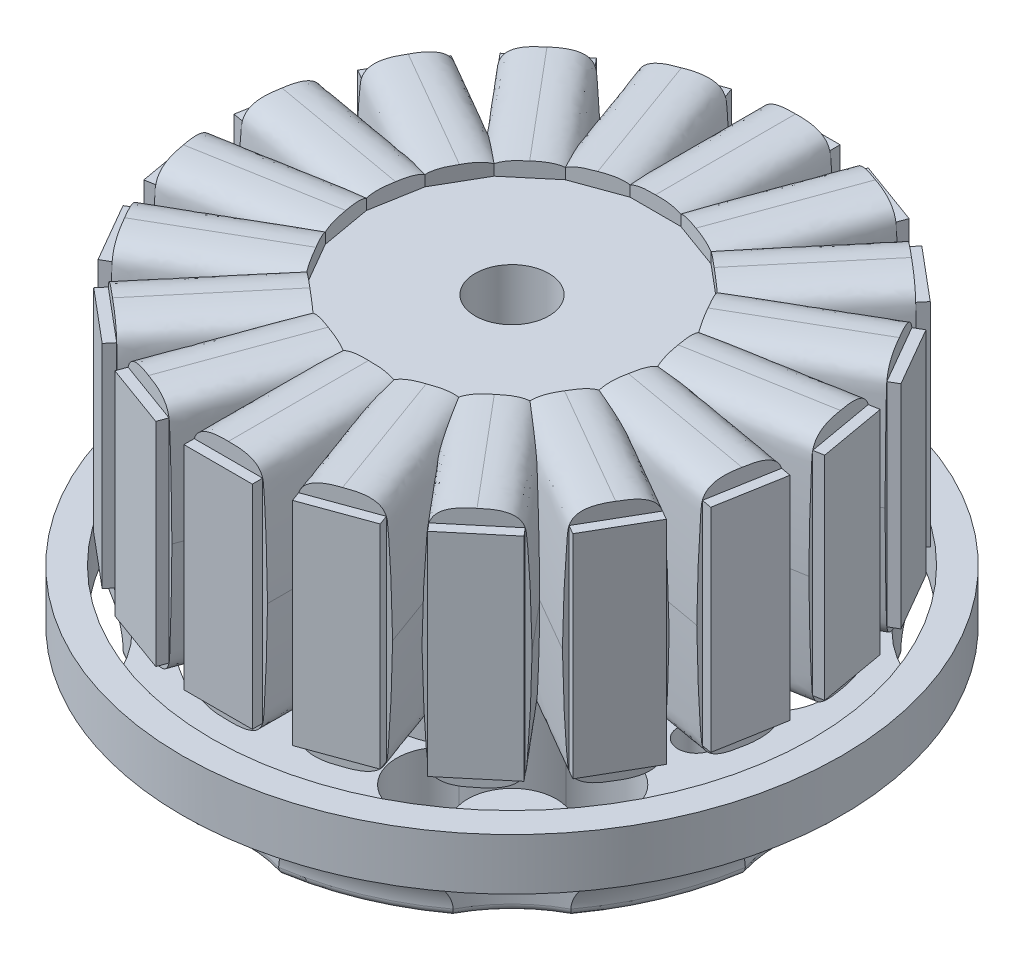
SolidWorks part; units mm, degrees
ref_plane "Front Plane" through (0, 0, 0) normal (0, 0, 1) x (1, 0, 0)
ref_plane "Top Plane" through (0, 0, 0) normal (0, 1, 0) x (1, 0, 0)
ref_plane "Right Plane" through (0, 0, 0) normal (1, 0, 0) x (0, 0, -1)
sketch "Sketch1" plane through (0, 0, 0) normal (0, 1, 0) x (1, 0, 0)
  circle A0 centre (0, 0) radius 22.36
  dimension "D1" = 44.72
extrude "Boss-Extrude1" add sketch "Sketch1" against normal blind 7.5
sketch "Sketch4" plane through (0, 0, 0) normal (0, 0, 1) x (1, 0, 0)
  line L0 (-22.36, 0) -> (-22.36, -7.5) construction
  line L1 (0, 0) -> (0, -7.5) construction
  line L2 (-22.36, -7.5) -> (22.36, -7.5) construction
  circle A0 centre (-22.36, -7) radius 3.5
  point P0 (-22.36, -3.5)
  dimension "D2" = 7
  dimension "D1" = 3.5
revolve "Cut-Revolve1" cut sketch "Sketch4" angle 360 about L1
sketch "Sketch6" plane through (0, 0, 0) normal (0, 1, 0) x (1, 0, 0)
  circle A0 centre (0, 0) radius 20.36
  circle A1 centre (0, 0) radius 22.36 construction
  dimension "D1" = 2
extrude "Cut-Extrude3" cut sketch "Sketch6" against normal offset from surface (3.9 mm away) 3.6 up to face at (0, -7.5, -18.8959)
sketch "Sketch7" plane through (0, -3.9, 0) normal (0, 1, 0) x (1, 0, 0)
  circle A0 centre (0, 0) radius 10
  dimension "D1" = 20
extrude "Boss-Extrude2" add sketch "Sketch7" along normal blind 20.8
sketch "Sketch9" plane through (0, 16.9, 0) normal (0, 1, 0) x (1, 0, 0)
  line L0 (0, 0) -> (0, 30.8814) construction
  line L2 (-2.32, 19.93) -> (2.32, 19.93)
  line L3 (-2.32, 19.93) -> (-2.32, 19.23)
  line L4 (-2.32, 19.23) -> (-0.3439, 19.23)
  line L5 (2.32, 19.93) -> (2.32, 19.23)
  line L6 (-2.32, 19.93) -> (2.32, 19.23) construction
  line L7 (-2.32, 19.23) -> (2.32, 19.93) construction
  line L16 (16.0999, 11.9742) -> (15.4937, 11.6242)
  line L75 (0.3439, 19.23) -> (2.32, 19.23)
  line L77 (-0.35, 19.23) -> (-0.35, 9.9939)
  line L79 (0.35, 19.23) -> (0.35, 9.9939)
  line L133 (-19.3407, 1.0545) -> (-18.9986, 2.9946) [skipped]
  line L134 (-20.0301, 1.1761) -> (-19.2244, 5.7456) [skipped]
  line L135 (-19.2244, 5.7456) -> (-18.535, 5.624) [skipped]
  line L136 (-20.0301, 1.1761) -> (-19.3407, 1.0545) [skipped]
  line L137 (-18.4199, 7.9558) -> (-17.8137, 7.6058) [skipped]
  line L138 (-18.4199, 7.9558) -> (-16.0999, 11.9742) [skipped]
  line L139 (-16.0999, 11.9742) -> (-15.4937, 11.6242) [skipped]
  line L140 (-17.8137, 7.6058) -> (-16.8287, 9.3119) [skipped]
  line L141 (-14.588, 13.776) -> (-14.138, 13.2398) [skipped]
  line L142 (-14.138, 13.2398) -> (-12.6289, 14.5061) [skipped]
  line L143 (-14.588, 13.776) -> (-11.0335, 16.7585) [skipped]
  line L144 (-11.0335, 16.7585) -> (-10.5836, 16.2223) [skipped]
  line L145 (-8.7571, 17.2768) -> (-6.9059, 17.9506) [skipped]
  line L146 (-8.9965, 17.9346) -> (-4.6364, 19.5216) [skipped]
  line L147 (-4.6364, 19.5216) -> (-4.397, 18.8638) [skipped]
  line L148 (-8.9965, 17.9346) -> (-8.7571, 17.2768) [skipped]
  line L161 (4.397, 18.8638) -> (6.2482, 18.19) [skipped]
  line L162 (4.6364, 19.5216) -> (8.9965, 17.9346) [skipped]
  line L163 (11.0335, 16.7585) -> (10.5836, 16.2223) [skipped]
  line L164 (11.0335, 16.7585) -> (14.588, 13.776) [skipped]
  line L165 (16.0999, 11.9742) -> (18.4199, 7.9558) [skipped]
  line L166 (18.4199, 7.9558) -> (17.8137, 7.6058) [skipped]
  line L167 (15.4937, 11.6242) -> (16.4787, 9.9181) [skipped]
  line L168 (19.2244, 5.7456) -> (18.535, 5.624) [skipped]
  line L169 (19.2244, 5.7456) -> (20.0301, 1.1761) [skipped]
  line L170 (19.3407, -1.0545) -> (18.9986, -2.9946) [skipped]
  line L171 (20.0301, -1.1761) -> (19.2244, -5.7456) [skipped]
  line L172 (19.2244, -5.7456) -> (18.535, -5.624) [skipped]
  line L187 (14.138, -13.2398) -> (12.6289, -14.5061) [skipped]
  line L188 (14.588, -13.776) -> (11.0335, -16.7585) [skipped]
  line L189 (18.4199, -7.9558) -> (16.0999, -11.9742) [skipped]
  line L190 (17.8137, -7.6058) -> (16.8287, -9.3119) [skipped]
  line L191 (16.0999, -11.9742) -> (15.4937, -11.6242) [skipped]
  line L192 (2.32, -19.23) -> (-2.32, -19.23) [skipped]
  line L193 (-2.32, -19.93) -> (-2.32, -19.23) [skipped]
  line L194 (-4.397, -18.8638) -> (-8.7571, -17.2768) [skipped]
  line L195 (-4.6364, -19.5216) -> (-8.9965, -17.9346) [skipped]
  line L196 (-11.0335, -16.7585) -> (-10.5836, -16.2223) [skipped]
  line L197 (-10.5836, -16.2223) -> (-14.138, -13.2398) [skipped]
  line L198 (-16.0999, -11.9742) -> (-18.4199, -7.9558) [skipped]
  line L199 (-19.2244, -5.7456) -> (-20.0301, -1.1761) [skipped]
  line L200 (-20.0301, -1.1761) -> (-19.3407, -1.0545) [skipped]
  line L201 (-18.535, -5.624) -> (-18.8771, -3.6839) [skipped]
  line L202 (-18.4199, -7.9558) -> (-17.8137, -7.6058) [skipped]
  line L203 (-15.4937, -11.6242) -> (-16.4787, -9.9181) [skipped]
  line L204 (-16.0999, -11.9742) -> (-15.4937, -11.6242) [skipped]
  line L205 (-14.588, -13.776) -> (-14.138, -13.2398) [skipped]
  line L206 (-11.0335, -16.7585) -> (-14.588, -13.776) [skipped]
  line L207 (-8.9965, -17.9346) -> (-8.7571, -17.2768) [skipped]
  line L208 (-19.2244, -5.7456) -> (-18.535, -5.624) [skipped]
  line L209 (-4.6364, -19.5216) -> (-4.397, -18.8638) [skipped]
  line L210 (2.32, -19.93) -> (-2.32, -19.93) [skipped]
  line L211 (2.32, -19.93) -> (2.32, -19.23) [skipped]
  line L212 (8.9965, -17.9346) -> (4.6364, -19.5216) [skipped]
  line L213 (8.7571, -17.2768) -> (4.397, -18.8638) [skipped]
  line L214 (4.7854, -19.9309) -> (4.397, -18.8638) [skipped]
  line L215 (11.0335, -16.7585) -> (10.5836, -16.2223) [skipped]
  line L216 (8.9965, -17.9346) -> (8.7571, -17.2768) [skipped]
  line L217 (14.588, -13.776) -> (14.138, -13.2398) [skipped]
  line L218 (18.4199, -7.9558) -> (17.8137, -7.6058) [skipped]
  line L219 (20.0301, -1.1761) -> (19.3407, -1.0545) [skipped]
  line L220 (20.0301, 1.1761) -> (19.3407, 1.0545) [skipped]
  line L221 (18.535, 5.624) -> (18.8771, 3.6839) [skipped]
  line L222 (4.6364, 19.5216) -> (4.397, 18.8638) [skipped]
  line L223 (8.9965, 17.9346) -> (8.7571, 17.2768) [skipped]
  line L224 (10.5836, 16.2223) -> (12.0927, 14.956) [skipped]
  line L225 (14.588, 13.776) -> (14.138, 13.2398) [skipped]
  arc A2 (0.35, 9.9939) -> (-0.35, 9.9939) centre (0, 0) ccw
  point P3 (0, 19.58)
  point P10 (0, 12.4867)
  point P79 (0, 0)
  point P156 (0, 0)
  circle M73 centre (0, 0) radius 10
  dimension "D1" = 0.7
  dimension "D2" = 4.64
  dimension "D3" = 19.58
  dimension "D4" = 18
extrude "Boss-Extrude3" add sketch "Sketch9" against normal offset from surface (15.4 mm away) 1.5 contours M73 | L79 L75 L5 L2 L3 L4 L77 M73 region at (0, 16.9, -16.275) region at (0, 16.9, 0) up to face at (0, 0, 20.36)
pattern_circular "CirPattern1" count 18 over 360 about axis through (0, 16.9, 0) along (0, -1, 0) of "Boss-Extrude3"
sketch "Sketch10" plane through (0, 16.9, 0) normal (0, 1, 0) x (1, 0, 0)
  circle A0 centre (0, 0) radius 24.3732
extrude "Cut-Extrude4" cut sketch "Sketch10" against normal blind 1
sketch "Sketch11" plane through (0, -7.5, 0) normal (0, -1, 0) x (1, 0, 0)
  circle A0 centre (0, 0) radius 8
  dimension "D1" = 16
extrude "Cut-Extrude5" cut sketch "Sketch11" against normal blind 0.2
sketch "Sketch12" plane through (0, -7.3, 0) normal (0, -1, 0) x (-1, 0, 0)
  circle A0 centre (0, 0) radius 3.75
  circle A1 centre (0, 0) radius 2.5
  dimension "D1" = 7.5
  dimension "D2" = 5
extrude "Boss-Extrude4" add sketch "Sketch12" along normal blind 0.2
sketch "Sketch13" plane through (0, -7.3, 0) normal (0, -1, 0) x (1, 0, 0)
  circle A0 centre (0, 0) radius 2.5
extrude "Cut-Extrude6" cut sketch "Sketch13" against normal blind 41.2
sketch "Sketch14" plane through (0, -7.5, 0) normal (0, -1, 0) x (-1, 0, 0)
  line L0 (0, 0) -> (0, -25.6549) construction
  line L1 (0, 0) -> (-22.5396, -22.5396) construction
  line L2 (0, 0) -> (-26.5501, 0) construction
  circle A0 centre (0, -12.5) radius 1.25
  circle A1 centre (-12.5, 0) radius 1.25
  circle A2 centre (0, 12.5) radius 1.25
  circle A3 centre (12.5, 0) radius 1.25
  circle A4 centre (-11.3137, -11.3137) radius 1
  circle A5 centre (-4.1411, 15.4548) radius 1
  circle A6 centre (15.4548, -4.1411) radius 1
  circle A7 centre (0, 0) radius 22.36 construction
  circle A8 centre (-27.861, 0) radius 9.6379
  circle A9 centre (-19.7007, 19.7007) radius 9.6379
  circle A10 centre (0, 27.861) radius 9.6379
  circle A11 centre (19.7007, 19.7007) radius 9.6379
  circle A12 centre (27.861, 0) radius 9.6379
  circle A13 centre (19.7007, -19.7007) radius 9.6379
  circle A14 centre (0, -27.861) radius 9.6379
  circle A15 centre (-19.7007, -19.7007) radius 9.6379
  point P14 (0, 0)
  point P15 (-18.5, 0)
  point P16 (-19.8003, 10.3884)
  point P17 (-21.236, 7)
  point P22 (0, 0)
  point P24 (-21.236, -7)
  point P41 (0, 0)
  point P47 (0, 0)
  dimension "D1" = 2.5
  dimension "D5" = 2
  dimension "D2" = 12.5
  dimension "D4" = 45
  dimension "D6" = 16
  dimension "D8" = 18.5
  dimension "D9" = 7
  dimension "D10" = 7
  dimension "D12" = 3.68
  dimension "D3" = 4
  dimension "D7" = 3
  dimension "D11" = 8
extrude "Cut-Extrude7" cut sketch "Sketch14" against normal blind 4
sketch "Sketch15" plane through (0, -7.5, 0) normal (0, -1, 0) x (-1, 0, 0)
  line L0 (0, 0) -> (0, -18.223) construction
  line L1 (0, 0) -> (-11.3137, -11.3137) construction
  line L2 (0, 0) -> (-12.5, 0) construction
  line L3 (0, 0) -> (-4.1411, 15.4548) construction
  line L4 (0, 0) -> (10.251, -2.7468) construction
  line L5 (12.557, -3.3646) -> (15.4548, -4.1411) construction
  arc A0 (2.905, -18.6713) -> (-2.905, -18.6713) centre (0, -27.861) ccw construction
  arc A1 (-8.6571, -5.0055) -> (-5.0501, -8.6311) centre (0, 0) ccw
  arc A2 (10.6792, -3.4673) -> (8.6838, -4.959) centre (11.3975, -6.5086) ccw
  arc A3 (10.6792, -3.4673) -> (12.5009, -4.6651) centre (11.024, -4.9271) cw
  arc A4 (14.0447, 8.1737) -> (8.1473, 14.06) centre (0, 0) ccw
  arc A5 (12.5009, -4.6651) -> (13.5648, -6.4709) centre (15.4548, -4.1411) ccw
  arc A6 (4.9724, -8.6761) -> (8.0802, -14.0987) centre (6.5263, -11.3874) ccw
  arc A7 (8.0802, -14.0987) -> (13.9031, -8.4122) centre (0, 0) ccw
  circle A8 centre (0, -12.5) radius 3.55 construction
  arc A9 (-8.6761, 4.9724) -> (-14.0987, 8.0802) centre (-11.3874, 6.5263) cw
  circle A10 centre (0, 12.5) radius 3.55 construction
  circle A11 centre (-12.5, 0) radius 3.55 construction
  circle A12 centre (-4.1411, 15.4548) radius 3 construction
  arc A13 (-8.5024, -12.3608) -> (-12.3698, -8.5057) centre (-11.3137, -11.3137) ccw
  arc A14 (8.6429, 5.03) -> (14.0447, 8.1737) centre (11.3438, 6.6018) ccw
  arc A15 (8.1473, 14.06) -> (5.0137, 8.6523) centre (6.5805, 11.3562) ccw
  arc A16 (-8.6761, 4.9724) -> (-4.959, 8.6838) centre (0, 0) cw
  arc A17 (13.5648, -6.4709) -> (13.9031, -8.4122) centre (12.6198, -7.6357) cw
  arc A18 (-7.5291, -14.3207) -> (-5.0501, -8.6311) centre (-6.6283, -11.3284) ccw
  arc A19 (-8.6571, -5.0055) -> (-14.3152, -7.5929) centre (-11.3624, -6.5697) ccw
  arc A20 (-3.4673, 10.6792) -> (-4.959, 8.6838) centre (-6.5086, 11.3975) cw
  arc A21 (-3.4673, 10.6792) -> (-4.6651, 12.5009) centre (-4.9271, 11.024) ccw
  arc A22 (11.4264, -3.3838) -> (8.6838, -4.959) centre (11.3975, -6.5086) ccw
  arc A23 (-7.5291, -14.3207) -> (-8.5024, -12.3608) centre (-7.0967, -12.8844) cw
  arc A24 (-14.3152, -7.5929) -> (-12.3698, -8.5057) centre (-12.8979, -7.1018) ccw
  arc A25 (4.9724, -8.6761) -> (8.6838, -4.959) centre (0, 0) ccw
  arc A26 (8.6429, 5.03) -> (5.0137, 8.6523) centre (0, 0) ccw
  arc A27 (-4.6651, 12.5009) -> (-6.4709, 13.5648) centre (-4.1411, 15.4548) cw
  arc A28 (-6.4709, 13.5648) -> (-8.4122, 13.9031) centre (-7.6357, 12.6198) ccw
  arc A29 (-14.0987, 8.0802) -> (-8.4122, 13.9031) centre (0, 0) cw
  dimension "D1" = 1.5
  dimension "D2" = 32.5
  dimension "D3" = 7.1
  dimension "D4" = 6
  dimension "D5" = 6
  dimension "D6" = 6
  dimension "D7" = 1.5
  dimension "D8" = 1.5
extrude "Cut-Extrude8" cut sketch "Sketch15" against normal blind 10 contours A25 A6 A7 A17 A5 A3 A2 | A26 A14 A4 A15 | A29 A9 A16 A20 A21 A27 A28 | A19 A24 A13 A23 A18 A1 region at (8.7248, -7.5, 8.663) region at (-8.8033, -7.5, 9.3248) region at (-9.0821, -7.5, -9.0991) region at (9.3248, -7.5, -8.8033)
sketch "Sketch16" plane through (16.6537, 0, -9.615) normal (-0.866, 0, 0.5) x (0.5, 0, 0.866)
  line L0 (0, 0) -> (0, 19.8608) construction
  line L2 (0, 8.7) -> (-2.32, 8.7) construction
  line L3 (-2.32, 1.5) -> (-2.32, 15.9) construction
  line L4 (2.32, 15.9) -> (-2.32, 15.9) construction
  line L5 (0, 8.7) -> (-6.2589, 8.7) construction
  spline S0 degree 3 poles (0, 16.9) (-1.5748, 16.9453) (-2.3432, 16.2444) (-2.5141, 13.7773) (-2.6305, 11.0743) (-2.65, 8.7) knots 0 0 0 0 0.099934 0.155486 0.555519 0.555519 0.555519 0.555519
  spline S1 degree 3 poles (0, 0.5) (-1.5748, 0.4547) (-2.3432, 1.1556) (-2.5141, 3.6227) (-2.6305, 6.3257) (-2.65, 8.7) knots 0 0 0 0 0.099934 0.155486 0.555519 0.555519 0.555519 0.555519
  spline S2 degree 3 poles (0, 0.5) (1.5748, 0.4547) (2.3432, 1.1556) (2.5141, 3.6227) (2.6305, 6.3257) (2.65, 8.7) knots 0 0 0 0 0.099934 0.155486 0.555519 0.555519 0.555519 0.555519
  spline S3 degree 3 poles (0, 16.9) (1.5748, 16.9453) (2.3432, 16.2444) (2.5141, 13.7773) (2.6305, 11.0743) (2.65, 8.7) knots 0 0 0 0 0.099934 0.155486 0.555519 0.555519 0.555519 0.555519
  point P5 (-2.65, 8.7)
  point P6 (0, 16.9)
  point P7 (-2.32, 15.9)
  dimension "D1" = 1
  dimension "D2" = 2.65
extrude "Boss-Extrude5" add sketch "Sketch16" along normal blind 9.5
pattern_circular "CirPattern4" count 18 over 360 about axis through (0, 16.9, 0) along (0, -1, 0) of "Boss-Extrude5"
fillet "Fillet2" radius 0.5 16 edges at (-12.8856, -7.5, 12.8856) (0, -7.5, 18.223) (12.8856, -7.5, 12.8856) (18.223, -7.5, 0) (12.8856, -7.5, -12.8856) (0, -7.5, -18.223) (-12.8856, -7.5, -12.8856) (-18.223, -7.5, 0) (-17.4575, -7.5, 7.2311) (-17.4575, -7.5, -7.2311) (-7.2311, -7.5, -17.4575) (7.2311, -7.5, -17.4575) (17.4575, -7.5, -7.2311) (17.4575, -7.5, 7.2311) (-7.2311, -7.5, 17.4575) (7.2311, -7.5, 17.4575)
